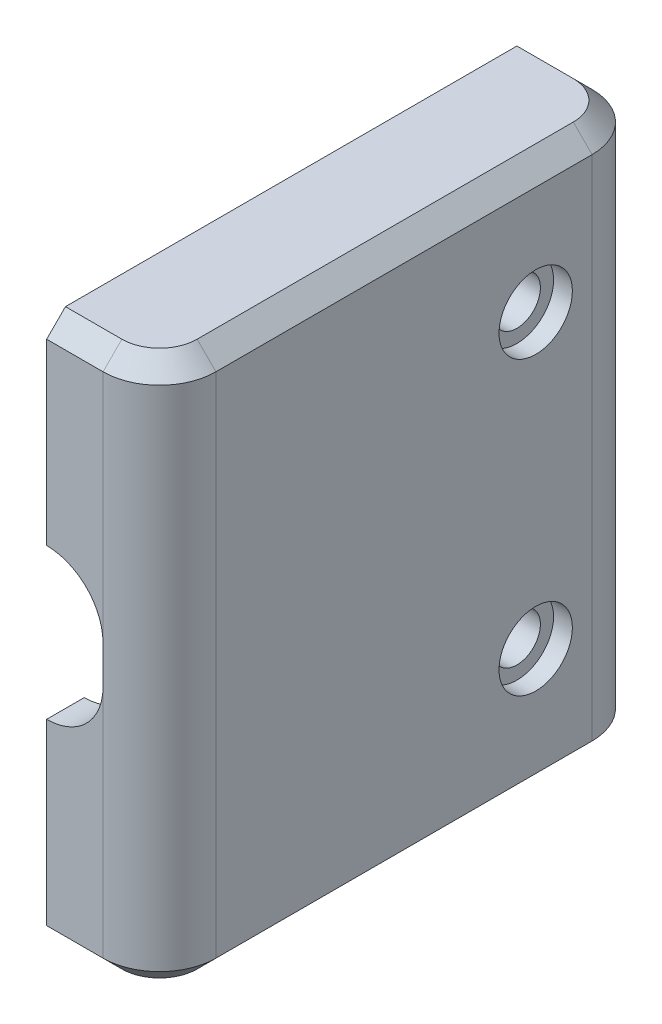
SolidWorks part; units mm, degrees
ref_plane "Спереди" through (0, 0, 0) normal (0, 0, 1) x (1, 0, 0)
ref_plane "Сверху" through (0, 0, 0) normal (0, 1, 0) x (1, 0, 0)
ref_plane "Справа" through (0, 0, 0) normal (1, 0, 0) x (0, 0, -1)
sketch "Эскиз1" plane through (0, 0, 0) normal (1, 0, 0) x (0, 0, -1)
  line L1 (-13, 14.5) -> (13, 14.5)
  line L2 (-13, 14.5) -> (-13, -14.5)
  line L3 (-13, -14.5) -> (13, -14.5)
  line L4 (13, 14.5) -> (13, -14.5)
  line L5 (-13, 14.5) -> (13, -14.5) construction
  line L6 (-13, -14.5) -> (13, 14.5) construction
  point P0 (0, 0)
  dimension "D1" = 26
  dimension "D2" = 29
extrude "Бобышка-Вытянуть1" add sketch "Эскиз1" along normal blind 6
sketch "Эскиз2" plane through (0, 0, 0) normal (-1, 0, 0) x (0, 0, 1)
  line L0 (-13, 0) -> (13, 0) construction
  line L1 (-13, -14.5) -> (-13, 14.5) construction
  line L2 (13, 14.5) -> (13, -14.5) construction
  circle A0 centre (-7, 7.75) radius 1.25
  circle A1 centre (-7, -7.75) radius 1.25
  dimension "D2" = 2.5
  dimension "D1" = 6
  dimension "D3" = 15.5
extrude "Вырез-Вытянуть1" cut sketch "Эскиз2" against normal through all
sketch "Эскиз4" plane through (0, 0, 0) normal (-1, 0, 0) x (0, 0, 1)
  line L0 (-13, 14.5) -> (13, 14.5) construction
  line L1 (5, 11.5) -> (-11, 11.5)
  line L2 (5, 11.5) -> (5, -11.5)
  line L3 (5, -11.5) -> (-11, -11.5)
  line L4 (-11, 11.5) -> (-11, -11.5)
  line L5 (5, 11.5) -> (-11, -11.5) construction
  line L6 (5, -11.5) -> (-11, 11.5) construction
  line L7 (-13, -14.5) -> (-13, 14.5) construction
  line L8 (13, 14.5) -> (13, -14.5) construction
  point P0 (-3, 0)
  dimension "D1" = 3
  dimension "D2" = 2
  dimension "D3" = 8
extrude "Вырез-Вытянуть3" cut sketch "Эскиз4" against normal blind 2
sketch "Эскиз5" plane through (2, 0, 0) normal (-1, 0, 0) x (0, 0, 1)
  line L0 (-11, -3.5) -> (-11, 3.5)
  line L1 (-11, 11.5) -> (-11, -11.5) construction
  line L2 (-11, 3.5) -> (-6, 3.5)
  line L3 (-6, 3.5) -> (-6, 10.5)
  line L4 (-6, 10.5) -> (5, 10.5)
  line L5 (5, -11.5) -> (5, 11.5) construction
  line L6 (5, 10.5) -> (5, -10.5)
  line L7 (-11, 0) -> (5, 0) construction
  line L8 (-11, 11.5) -> (-11, -11.5) construction
  line L11 (-6, -10.5) -> (5, -10.5)
  line L12 (-6, -3.5) -> (-6, -10.5)
  line L13 (-11, -3.5) -> (-6, -3.5)
  dimension "D1" = 5
  dimension "D2" = 7
  dimension "D3" = 21
extrude "Вырез-Вытянуть4" cut sketch "Эскиз5" against normal blind 1.5
fillet "Скругление1" radius 1 8 edges at (2.75, 3.5, -6) (2.75, 3.5, -11) (2.75, -3.5, -11) (2.75, -3.5, -6) (2.75, -8.5, -6) (2.75, -7, -6) (2.75, 7, -6) (2.75, 8.5, -6)
sketch "Эскиз6" plane through (6, 0, 0) normal (1, 0, 0) x (0, 0, -1)
  circle A0 centre (7, 7.75) radius 1.95
  circle A1 centre (7, -7.75) radius 1.95
  dimension "D1" = 3.9
  dimension "D2" = 3.9
extrude "Вырез-Вытянуть5" cut sketch "Эскиз6" against normal blind 1
fillet "Скругление3" radius 3 2 edges at (6, 0, 13) (6, 0, -13)
sketch "Эскиз8" plane through (0, 0, 0) normal (-1, 0, 0) x (0, 0, 1)
  line L0 (5, -11.5) -> (5, 11.5) construction
  line L1 (11, 10.5) -> (5, 10.5)
  line L2 (11, 10.5) -> (11, -10.5)
  line L3 (11, -10.5) -> (5, -10.5)
  line L4 (5, 10.5) -> (5, -10.5)
  line L5 (11, 10.5) -> (5, -10.5) construction
  line L6 (11, -10.5) -> (5, 10.5) construction
  line L7 (13, 14.5) -> (13, -14.5) construction
  line L8 (5, 10.5) -> (-6, 10.5) construction
  line L9 (-6, -10.5) -> (5, -10.5) construction
  point P0 (8, 0)
  dimension "D1" = 2
extrude "Вырез-Вытянуть6" cut sketch "Эскиз8" against normal up to surface (3.5 mm away) up to face at (3.5, 0, -5.9336)
fillet "Скругление2" radius 1 8 edges at (1, -11.5, -11) (1, -11.5, 5) (2.75, -10.5, -6) (1, 11.5, -11) (1, 11.5, 5) (2.75, 10.5, -6) (1.75, -10.5, 11) (1.75, 10.5, 11)
fillet "Скругление4" radius 1 2 edges at (1, -10.5, 5) (1, 10.5, 5)
sketch "Эскиз9" plane through (0, 0, 11) normal (0, 0, -1) x (-1, 0, 0)
  line L1 (3, 4) -> (-3, 4)
  line L2 (3, 4) -> (3, -4)
  line L3 (3, -4) -> (-3, -4)
  line L4 (-3, 4) -> (-3, -4)
  line L5 (3, 4) -> (-3, -4) construction
  line L6 (3, -4) -> (-3, 4) construction
  line L8 (0, -14.5) -> (0, 14.5) construction
  point P0 (0, 0)
  dimension "D1" = 8
  dimension "D2" = 3
extrude "Вырез-Вытянуть7" cut sketch "Эскиз9" against normal up to next
fillet "Скругление5" radius 3 2 edges at (3, -4, 12) (3, 4, 12)
chamfer "Фаска2" distance 1 angle 45 10 edges at (1.5, 14.5, -13) (1.5, 14.5, 13) (5.1213, 14.5, -12.1213) (5.1213, 14.5, 12.1213) (6, 14.5, 0) (1.5, -14.5, 13) (1.5, -14.5, -13) (5.1213, -14.5, 12.1213) (5.1213, -14.5, -12.1213) (6, -14.5, 0)
equation "\"motor_diameter\"= 30"
equation "\"mm_diameter\"= IIF ( \"motor_diameter\" < 34 , 41 , \"motor_diameter\" + 8 )"
equation "\"upper_shafts_diameter\"= 5"
equation "\"upper_shats_length\"= 180"
equation "\"upper_bearing_d1\"= 10"
equation "\"upper_bearing_d2\"= 5"
equation "\"upper_bearing_h\"= 15"
equation "\"lower_shafts_diameter\"= 5"
equation "\"lower_shafts_length\"= 180"
equation "\"lower_bearing_d1\"= 10"
equation "\"lower_bearing_d2\"= 5"
equation "\"lower_bearing_h\"= 15"
equation "\"print_offset\"= 0.5"
equation "\"bh_screws_d\"= 2"
equation "\"bh_screws_h\"= 20"
equation "\"bh_screws_hh_d\"= 3.4"
equation "\"bh_screws_hh_h\"= 2"
equation "\"bh_nut_d\"= 3.8"
equation "\"bh_nut_h\"= 2"
equation "\"motor_screws_d\"= 3"
equation "\"motor_screws_h\"= 16"
equation "\"motor_screws_hh_d\"= 5.5"
equation "\"motor_screws_hh_h\"= 3"
equation "\"plate_hole_distance\"= 25.4"
equation "\"plate_screws_d\"= 6.5"
equation "\"shafts_diameter\"= IIF ( \"mm_diameter\" < 42 , 42 + 8 , \"mm_diameter\" + 8 )"
equation "\"central_hole_diameter\"= 8"
equation "\"bh_thikness\"= 4"
equation "\"ends_screws_d\"= 4"
equation "\"ends_screws_h\"= 16"
equation "\"ends_screws_hh_d\"= 6.7"
equation "\"ends_screws_hh_h\"= 4.1"
equation "\"ends_nut_d\"= 6.8"
equation "\"ends_nut_h\"= 3"
equation "\"system_radius\" = ( \"shafts_diameter\" + 12 + \"bh_thikness\" / 2 ) / 2"
equation "\"encoder_distance\"= \"system_radius\" + 4"
equation "\"tape_position\"= \"encoder_distance\" - 2 + 3.9 + 1.7 / 2"
equation "\"D2@Эскиз1\"=\"upper_bearing_h\"+\"bh_thikness\"*2+6"
equation "\"D2@Эскиз2\"=\"bh_screws_d\"+\"print_offset\""
equation "\"D1@Эскиз6\"=\"bh_screws_hh_d\"+\"print_offset\""
equation "\"D2@Эскиз6\"=\"D1@Эскиз6\""
